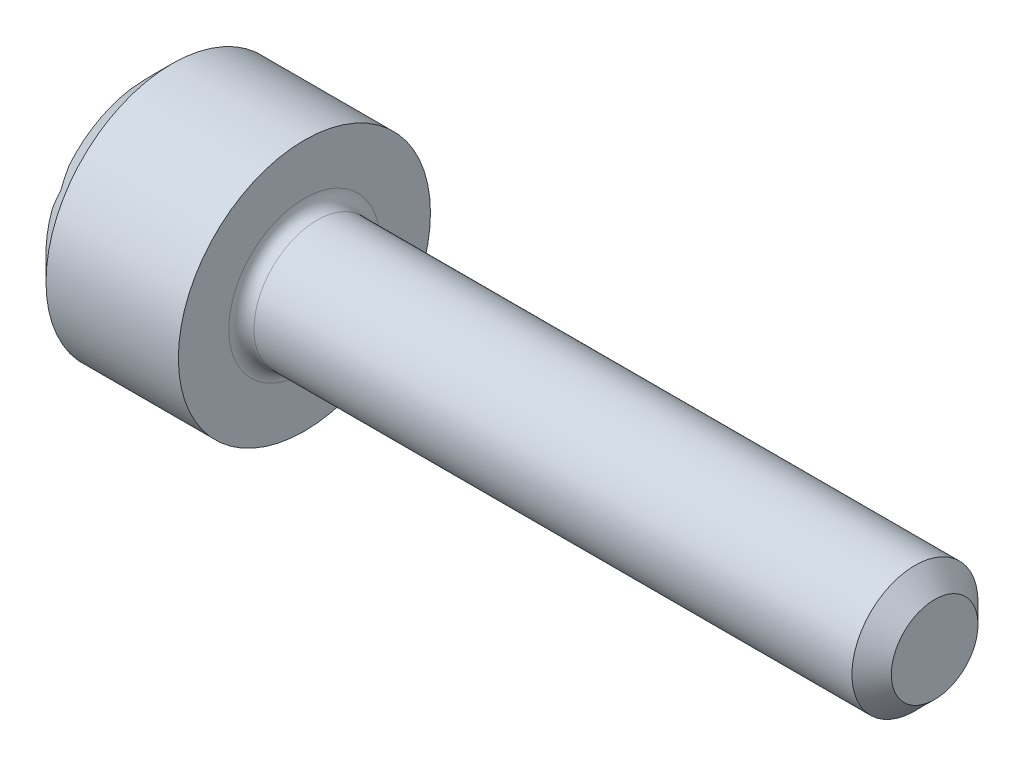
SolidWorks part; units mm, degrees
material "NA"
ref_plane "Front Plane" through (0, 0, 0) normal (0, 0, 1) x (1, 0, 0)
ref_plane "Top Plane" through (0, 0, 0) normal (0, 1, 0) x (1, 0, 0)
ref_plane "Right Plane" through (0, 0, 0) normal (1, 0, 0) x (0, 0, -1)
sketch "Sketch1" plane through (0, 0, 0) normal (0, 1, 0) x (1, 0, 0)
  line L0 (0, 0) -> (0, 4)
  line L1 (0, 4) -> (5, 4)
  line L2 (5, 4) -> (5, 2)
  line L3 (5, 2) -> (25, 2)
  line L4 (25, 2) -> (25, 0)
  line L5 (25, 0) -> (0, 0)
  dimension "16" = 5
  dimension "D2" = 4
  dimension "D3" = 2
  dimension "20" = 20
revolve "Revolve1" add sketch "Sketch1" angle 360 about L5
chamfer "Chamfer1" distance 0.625 angle 45 1 edges at (25, 0, -2)
sketch "Sketch3" plane through (0, 0, 0) normal (0, 1, 0) x (1, 0, 0)
  line L0 (0, 0) -> (5.7321, 0)
  line L1 (0, 4) -> (0, -4) construction
  line L2 (5.7321, 0) -> (4, 3)
  line L3 (4, 3) -> (0, 3)
  line L4 (0, 3) -> (0, 0)
  dimension "5" = 3
  dimension "D2" = 4
  dimension "D3" = 60
revolve "Cut-Revolve1" cut sketch "Sketch3" angle 360 about L0
sketch "Sketch2" plane through (0, 0, 0) normal (-1, 0, 0) x (0, 0, 1)
  line L0 (0, 0) -> (0, 3.4641) construction
  line L1 (0, 3.4641) -> (-3, 1.7321)
  line L2 (-3, 1.7321) -> (-3, -1.7321)
  line L3 (-3, -1.7321) -> (0, -3.4641)
  line L4 (0, -3.4641) -> (3, -1.7321)
  line L5 (3, -1.7321) -> (3, 1.7321)
  line L6 (3, 1.7321) -> (0, 3.4641)
  circle A0 centre (0, 0) radius 3 construction
  dimension "4" = 6
extrude "Cut-Extrude1" cut sketch "Sketch2" against normal blind 4 contours L4 L5 L6 L1 L2 L3
chamfer "Chamfer2" distance 0.8 angle 45 1 edges at (0, 0, -4)
fillet "Fillet1" radius 0.4 1 edges at (5, 0, -2)
ref_plane "Plane1" through (26.6, 0, 0) normal (1, 0, 0) x (0, 0, -1)
sketch "Sketch5" plane through (26.6, 0, 0) normal (1, 0, 0) x (0, 0, -1)
  circle A0 centre (0, 0) radius 4
  dimension "D1" = 8
curve "Helix/Spiral1" pitch 1.25 height 30 turns 24
sketch "Sketch6" plane through (0, 0, 0) normal (0, 0, 1) x (1, 0, 0)
  line L0 (25.9873, 4.1353) -> (26.6, 3.0524) construction
  line L1 (26.6, 3.0524) -> (27.2127, 4.1353) construction
  line L2 (27.2127, 4.1353) -> (25.9873, 4.1353) construction
  line L3 (26.6, 4.1353) -> (26.6, 3.0524) construction
  line L4 (26.0639, 4) -> (27.1361, 4)
  line L5 (26.0639, 4) -> (26.4469, 3.323)
  line L6 (26.7531, 3.323) -> (27.1361, 4)
  line L7 (26.7531, 3.323) -> (26.4469, 3.323)
  point P6 (26.6, 4)
  dimension "D1" = 59
  dimension "D2" = 0.677
  dimension "D3" = 0.1353
  dimension "D4" = 0.2706
sweep "Cut-Sweep2" [suppressed] cut profiles "Sketch6" path "Helix/Spiral1"
